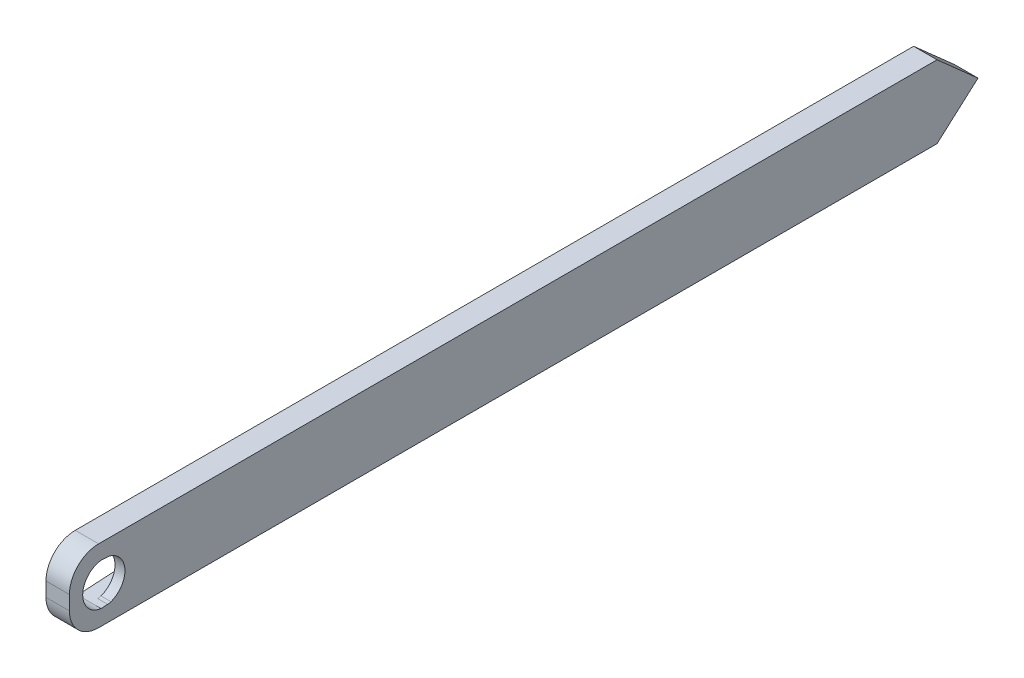
SolidWorks part; units mm, degrees
note: The reader was unsure of these and kept them because the rebuilt part matched: shared geometry of "Sketch7<3>".
material "Custom Plastic"
ref_plane "Front Plane" through (0, 0, 0) normal (0, 0, 1) x (1, 0, 0)
ref_plane "Top Plane" through (0, 0, 0) normal (0, 1, 0) x (1, 0, 0)
ref_plane "Right Plane" through (0, 0, 0) normal (1, 0, 0) x (0, 0, -1)
sketch "Sketch1" plane through (0, 0, 0) normal (1, 0, 0) x (0, 0, -1)
  line L1 (0, 0) -> (135.25, 0)
  line L2 (0, 0) -> (0, 12.42)
  line L3 (0, 12.42) -> (135.25, 12.42)
  line L6 (135.25, 0) -> (135.25, 12.42)
  line L7 (135.25, 12.42) -> (148.25, 12.42)
  line L8 (148.25, 12.42) -> (155.25, 6.21)
  line L9 (155.25, 6.21) -> (148.25, 0)
  line L10 (148.25, 0) -> (135.25, 0)
  point P6 (135.25, 6.21)
  point P8 (0, 0)
  dimension "D1" = 13
  dimension "D2" = 12.42
  dimension "D3" = 135.25
  dimension "D4" = 20
extrude "Boss-Extrude1" add sketch "Sketch1" along normal blind 4 contours L1 L6 L3 L2 | L10 L9 L8 L7 L6
sketch "Sketch7" plane through (0, 0, 0) normal (-1, 0, 0) x (0, 0, 1)
  line L0 (-5.4156, 9.79) -> (-23.4102, 8.715)
  line L1 (-23.4102, 3.705) -> (-5.4156, 2.63)
  line L2 (0, 0) -> (0, 12.42) construction
  line L3 (0, 12.42) -> (-148.25, 12.42) construction
  line L4 (-128.25, 0) -> (-128.25, 12.42) construction
  line L5 (0, 0) -> (-148.25, 0) construction
  circle A0 centre (-5.88, 6.21) radius 3.61
  arc A1 (-23.4102, 8.715) -> (-23.4102, 3.705) centre (-23.2605, 6.21) ccw
  point P6 (0, 6.21)
  point P8 (-5.88, 6.21)
  point P9 (57.9204, 6.21)
  point P12 (-45.1536, 6.21)
  dimension "D1" = 7.22
  dimension "D4" = 23.5
  dimension "D5" = 5.01
  dimension "D2" = 7.16
  dimension "D3" = 5.88
  dimension "D6" = 20
extrude "Cut-Extrude1" cut sketch "Sketch7" against normal through all contours A0
extrude "Cut-Extrude2" cut sketch "Sketch7<3>" against normal offset from surface (2.3 mm away) 1.7 contours L0 A1 L1 A0 up to face at (4, 6.21, -5.9857)
sketch "Sketch7<3>" plane through (0, 0, 0) normal (-1, 0, 0) x (0, 0, 1) same geometry as "Sketch7"
fillet "Fillet1" radius 5 2 edges at (2, 12.42, 0) (2, 0, 0)
fillet "Fillet2" radius 2 2 edges at (3.15, 2.7108, -6.7673) (3.15, 9.7092, -6.7673)
